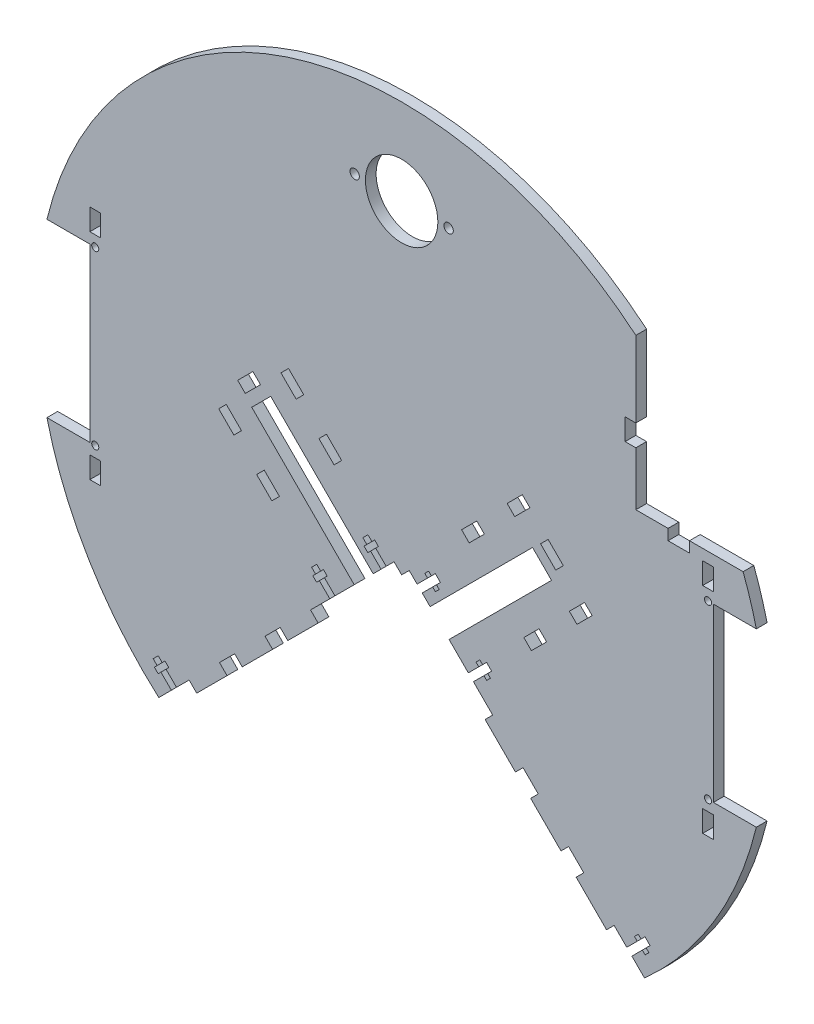
SolidWorks part; units mm, degrees
ref_plane "Front Plane" through (0, 0, 0) normal (0, 0, 1) x (1, 0, 0)
ref_plane "Top Plane" through (0, 0, 0) normal (0, 1, 0) x (1, 0, 0)
ref_plane "Right Plane" through (0, 0, 0) normal (1, 0, 0) x (0, 0, -1)
sketch "Sketch1" plane through (0, 0, 0) normal (0, 0, 1) x (1, 0, 0)
  circle A0 centre (0, 0) radius 215.9
  dimension "D1" = 431.8
extrude "Base Plate Extrusion" add sketch "Sketch1" along normal blind 6.35
sketch "Sketch2" plane through (0, 0, 6.35) normal (0, 0, 1) x (1, 0, 0)
  line L0 (0, 0) -> (0, -230.9791) construction
  line L1 (0, -17.4608) -> (143.6841, -161.1449)
  line L2 (0, -17.4608) -> (-143.6841, -161.1449)
  circle A1 centre (0, 0) radius 215.9 construction
  arc A2 (143.6841, -161.1449) -> (-143.6841, -161.1449) centre (0, 0) cw
  dimension "D1" = 90
  dimension "D2" = 203.2
extrude "V Funnel Cut" cut sketch "Sketch2" against normal through all
sketch "Sketch3" plane through (0, 0, 6.35) normal (0, 0, 1) x (1, 0, 0)
  line L0 (0, 0) -> (251.7982, 0) construction
  line L1 (209.8384, 50.8) -> (184.4384, 50.8)
  line L2 (209.8384, 50.8) -> (209.8384, -50.8)
  line L3 (209.8384, -50.8) -> (184.4384, -50.8)
  line L4 (184.4384, 50.8) -> (184.4384, -50.8)
  arc A0 (143.6841, -161.1449) -> (-143.6841, -161.1449) centre (0, 0) ccw construction
  arc A1 (209.8384, 50.8) -> (209.8384, -50.8) centre (0, 0) cw
  arc M7 (143.6841, -161.1449) -> (-143.6841, -161.1449) centre (0, 0) ccw
  dimension "D1" = 25.4
  dimension "D2" = 101.6
extrude "Wheel Track Cut" cut sketch "Sketch3" against normal through all contours L2 L0 A1 | L4 L0 L2 L1 | L0 L4 L3 L2 | L0 L2 M7 region at (197.1384, 25.4, 6.35) region at (197.1384, -25.4, 6.35) region at (212.266, 19.0862, 6.35) region at (212.266, -19.0862, 6.35)
mirror "Wheel Track Cut Mirror" about plane through (0, 0, 0) normal (1, 0, 0) of "Wheel Track Cut"
sketch "Sketch4" plane through (0, 0, 6.35) normal (0, 0, 1) x (1, 0, 0)
  line L0 (88.68, 15.0926) -> (77.4547, 26.3179)
  line L1 (88.68, 15.0926) -> (28.0633, -45.5241)
  line L2 (77.4547, 26.3179) -> (16.838, -34.2988)
  line L3 (28.0633, -45.5241) -> (16.838, -34.2988)
  line L4 (84.3174, 21.9553) -> (56.956, -5.4061) construction
  line L5 (65.1069, -1.7454) -> (69.5826, 2.7303) construction
  line L6 (65.0924, 7.2204) -> (60.6167, 2.7447) construction
  line L7 (143.6841, -161.1449) -> (0, -17.4608) construction
  dimension "D1" = 15.875
  dimension "D2" = 85.725
extrude "Cut-Extrude3" cut sketch "Sketch4" against normal through all
sketch "Sketch5" plane through (0, 0, 6.35) normal (0, 0, 1) x (1, 0, 0)
  line L0 (-4.4901, -21.951) -> (0, -17.4608)
  line L1 (-4.4901, -21.951) -> (0, -26.4411)
  line L2 (0, -17.4608) -> (4.4901, -21.951)
  line L3 (0, -26.4411) -> (4.4901, -21.951)
  line L4 (0, -17.4608) -> (-143.6841, -161.1449) construction
  line L6 (4.4901, -21.951) -> (0, -26.4411) construction
  dimension "D1" = 6.35
extrude "Boss-Extrude2" add sketch "Sketch5" against normal up to surface (6.35 mm away) up to face at (14.0691, -14.8765, 0)
mirror "Mirror2" about plane through (0, 0, 0) normal (1, 0, 0) of "Cut-Extrude3"
sketch "Sketch6" plane through (8.7304, -8.7304, 0) normal (0.7071, -0.7071, 0) x (0, 0, -1)
  line L0 (-6.35, -52.0342) -> (-6.35, -215.5467) construction
  line L1 (-6.35, -190.1467) -> (0, -190.1467)
  line L2 (-6.35, -190.1467) -> (-6.35, -164.7467)
  line L3 (-6.35, -164.7467) -> (0, -164.7467)
  line L4 (0, -190.1467) -> (0, -164.7467)
  line L5 (0, -52.0342) -> (0, -215.5467) construction
  dimension "D1" = 25.4
  dimension "D2" = 25.4
extrude "Boss-Extrude3" add sketch "Sketch6" along normal blind 6.35
pattern_linear "LPattern1" count 3 spacing 38.1 along (0.7071, 0.7071, 0) of "Boss-Extrude3"
sketch "Sketch7" plane through (-8.7304, -8.7304, 0) normal (-0.7071, -0.7071, 0) x (0, 0, 1)
  line L0 (6.35, -215.5467) -> (6.35, -52.0342) construction
  line L1 (6.35, -164.7467) -> (0, -164.7467)
  line L2 (6.35, -164.7467) -> (6.35, -190.1467)
  line L3 (6.35, -190.1467) -> (0, -190.1467)
  line L4 (0, -164.7467) -> (0, -190.1467)
  line L5 (0, -215.5467) -> (0, -52.0342) construction
  dimension "D1" = 25.4
  dimension "D2" = 25.4
extrude "Boss-Extrude4" add sketch "Sketch7" along normal blind 6.35
pattern_linear "LPattern2" count 3 spacing 38.1 along (-0.7071, 0.7071, 0) of "Boss-Extrude4"
sketch "Sketch8" plane through (0, 0, 0) normal (0, 0, -1) x (-1, 0, 0)
  line L0 (-72.2911, -22.4) -> (-81.2713, -13.4197)
  line L1 (-81.2713, -13.4197) -> (-85.7614, -17.9098)
  line L2 (-85.7614, -17.9098) -> (-76.7812, -26.8901)
  line L3 (-76.7812, -26.8901) -> (-72.2911, -22.4)
  line L4 (-99.2318, 4.5408) -> (-103.722, 0.0507)
  line L5 (-103.722, 0.0507) -> (-112.7022, 9.0309)
  line L6 (-112.7022, 9.0309) -> (-108.2121, 13.521)
  line L7 (-108.2121, 13.521) -> (-99.2318, 4.5408)
  line L8 (-95.6515, 26.0817) -> (-86.6712, 35.0619)
  line L9 (-86.6712, 35.0619) -> (-82.1811, 30.5718)
  line L10 (-82.1811, 30.5718) -> (-91.1613, 21.5915)
  line L11 (-91.1613, 21.5915) -> (-95.6515, 26.0817)
  line L12 (-66.9029, 36.8697) -> (-62.4128, 41.3598)
  line L13 (-62.4128, 41.3598) -> (-71.393, 50.3401)
  line L14 (-71.393, 50.3401) -> (-75.8832, 45.85)
  line L15 (-75.8832, 45.85) -> (-66.9029, 36.8697)
  line L16 (-48.9424, 18.9092) -> (-44.4523, 23.3993)
  line L17 (-44.4523, 23.3993) -> (-35.472, 14.4191)
  line L18 (-35.472, 14.4191) -> (-39.9621, 9.9289)
  line L19 (-39.9621, 9.9289) -> (-48.9424, 18.9092)
extrude "Cut-Extrude4" cut sketch "Sketch8" against normal blind 6.35
sketch "Sketch9" plane through (0, 0, 0) normal (0, 0, -1) x (-1, 0, 0)
  line L0 (-138.5621, 165.5698) -> (-138.5621, 76.2)
  line L1 (-138.5621, 76.2) -> (-202.0059, 76.2)
  line L2 (-132.2121, 76.2) -> (-157.6121, 76.2) construction
  line L3 (-138.5621, 152.4) -> (-138.5621, 120.65) construction
  arc A0 (209.8384, 50.8) -> (-209.8384, 50.8) centre (0, 0) ccw construction
  arc A1 (-202.0059, 76.2) -> (-138.5621, 165.5698) centre (0, 0) cw
extrude "Cut-Extrude5" cut sketch "Sketch9" against normal through all
sketch "Sketch10" plane through (0, 0, 0) normal (0, 0, -1) x (-1, 0, 0)
  line L0 (48.9424, 18.9092) -> (39.9621, 9.9289)
  line L1 (39.9621, 9.9289) -> (35.472, 14.4191)
  line L2 (35.472, 14.4191) -> (44.4523, 23.3993)
  line L3 (44.4523, 23.3993) -> (48.9424, 18.9092)
  line L4 (62.4128, 32.3796) -> (57.9227, 36.8697)
  line L5 (57.9227, 36.8697) -> (66.9029, 45.85)
  line L6 (66.9029, 45.85) -> (71.393, 41.3598)
  line L7 (71.393, 41.3598) -> (62.4128, 32.3796)
  line L8 (88.0065, 33.7266) -> (83.5144, 29.2385)
  line L9 (83.5144, 29.2385) -> (92.4966, 20.2562)
  line L10 (92.4966, 20.2562) -> (96.9868, 24.7464)
  line L11 (96.9868, 24.7464) -> (88.0065, 33.7266)
  line L12 (103.722, 9.0309) -> (94.7417, 0.0507)
  line L13 (94.7417, 0.0507) -> (99.2318, -4.4395)
  line L14 (99.2318, -4.4395) -> (108.2121, 4.5408)
  line L15 (108.2121, 4.5408) -> (103.722, 9.0309)
  line L16 (85.7614, -17.9098) -> (81.2713, -13.4197)
  line L17 (81.2713, -13.4197) -> (72.2911, -22.4)
  line L18 (72.2911, -22.4) -> (76.7812, -26.8901)
  line L19 (76.7812, -26.8901) -> (85.7614, -17.9098)
extrude "Cut-Extrude6" cut sketch "Sketch10" against normal blind 6.35
sketch "Sketch11" plane through (0, 0, 0) normal (0, 0, -1) x (-1, 0, 0)
  line L1 (184.4384, -69.85) -> (178.0884, -69.85)
  line L2 (184.4384, -69.85) -> (184.4384, -57.15)
  line L3 (184.4384, -57.15) -> (178.0884, -57.15)
  line L4 (178.0884, -69.85) -> (178.0884, -57.15)
  line L5 (184.4384, 57.15) -> (178.0884, 57.15)
  line L6 (184.4384, 57.15) -> (184.4384, 69.85)
  line L7 (184.4384, 69.85) -> (178.0884, 69.85)
  line L8 (178.0884, 57.15) -> (178.0884, 69.85)
  line L9 (-178.0884, -69.85) -> (-184.4384, -69.85)
  line L10 (-178.0884, -69.85) -> (-178.0884, -57.15)
  line L11 (-178.0884, -57.15) -> (-184.4384, -57.15)
  line L12 (-184.4384, -69.85) -> (-184.4384, -57.15)
  line L13 (-178.0884, 57.15) -> (-184.4384, 57.15)
  line L14 (-178.0884, 57.15) -> (-178.0884, 69.85)
  line L15 (-178.0884, 69.85) -> (-184.4384, 69.85)
  line L16 (-184.4384, 57.15) -> (-184.4384, 69.85)
extrude "Cut-Extrude7" cut sketch "Sketch11" against normal blind 6.35
sketch "Sketch12" plane through (0, 0, 0) normal (0, 0, -1) x (-1, 0, 0)
  line L0 (-202.0059, 76.2) -> (-138.5621, 76.2) construction
  line L1 (-157.6121, 69.85) -> (-170.284, 69.85)
  line L2 (-157.6121, 69.85) -> (-157.6121, 76.2)
  line L3 (-157.6121, 76.2) -> (-170.284, 76.2)
  line L4 (-170.284, 69.85) -> (-170.284, 76.2)
  line L5 (-138.5621, 76.2) -> (-138.5621, 165.5698) construction
  line L6 (-132.2121, 120.65) -> (-138.5621, 120.65)
  line L7 (-132.2121, 120.65) -> (-132.2121, 107.95)
  line L8 (-132.2121, 107.95) -> (-138.5621, 107.95)
  line L9 (-138.5621, 120.65) -> (-138.5621, 107.95)
  line L10 (-138.5621, 107.95) -> (-132.2121, 107.95) construction
extrude "Cut-Extrude8" cut sketch "Sketch12" against normal blind 6.35
sketch "Sketch13" plane through (0, 0, 6.35) normal (0, 0, 1) x (1, 0, 0)
  circle A0 centre (0, 165.1) radius 21.4313
  circle A1 centre (27.7813, 165.1) radius 2.7781
  circle A2 centre (-27.7812, 165.1) radius 2.7781
extrude "Cut-Extrude9" cut sketch "Sketch13" against normal through all
sketch "Sketch14" plane through (0, 0, 6.35) normal (0, 0, 1) x (1, 0, 0)
  line L0 (184.4384, 48.6664) -> (178.0884, 52.9336) construction
  line L1 (184.4384, 50.8) -> (184.4384, -50.8) construction
  line L2 (178.0884, 48.6664) -> (184.4384, 48.6664) construction
  line L3 (184.4384, 52.9336) -> (178.0884, 48.6664) construction
  line L4 (184.4384, -52.9336) -> (178.0884, -48.6664) construction
  line L5 (184.4384, -48.6664) -> (178.0884, -52.9336) construction
  line L6 (178.0884, -48.6664) -> (184.4384, -48.6664) construction
  circle A0 centre (181.2634, 50.8) radius 2.0955
  circle A1 centre (181.2634, -50.8) radius 2.0955
  dimension "D1" = 4.191
extrude "Cut-Extrude10" cut sketch "Sketch14" against normal through all
mirror "Mirror3" about plane through (0, 0, 0) normal (1, 0, 0) of "Cut-Extrude10"
sketch "Sketch15" plane through (0, 0, 6.35) normal (0, 0, 1) x (1, 0, 0)
  line L0 (-134.7038, -152.1647) -> (-152.6084, -134.2601) construction
  line L1 (-125.7236, -143.1844) -> (-143.6841, -161.1449) construction
  line L2 (-40.9724, -58.4333) -> (-60.7132, -38.6924) construction
  line L3 (-28.0633, -45.5241) -> (-53.8815, -71.3424) construction
  line L4 (-10.6641, -28.1249) -> (-27.2834, -11.5055) construction
  line L5 (-4.4901, -21.951) -> (-16.838, -34.2988) construction
  line B0 (-136.2125, -153.6734) -> (-133.1952, -150.656)
  line B1 (-141.6366, -142.2146) -> (-140.0022, -140.5801)
  line B2 (-140.0022, -140.5801) -> (-137.7571, -142.8252)
  line B3 (-137.7571, -142.8252) -> (-139.3915, -144.4596)
  line B4 (-139.3915, -144.4596) -> (-133.1952, -150.656)
  line B5 (-141.6366, -142.2146) -> (-143.9715, -139.8797)
  line B6 (-143.9715, -139.8797) -> (-146.9888, -142.8971)
  line B7 (-144.654, -145.2319) -> (-146.9888, -142.8971)
  line B8 (-142.4089, -147.477) -> (-136.2125, -153.6734)
  line B9 (-144.0433, -149.1114) -> (-142.4089, -147.477)
  line B10 (-146.2884, -146.8663) -> (-144.0433, -149.1114)
  line B11 (-144.654, -145.2319) -> (-146.2884, -146.8663)
  line B12 (-42.4811, -59.9419) -> (-39.4637, -56.9246)
  line B13 (-47.9052, -48.4831) -> (-46.2708, -46.8487)
  line B14 (-46.2708, -46.8487) -> (-44.0257, -49.0938)
  line B15 (-44.0257, -49.0938) -> (-45.6601, -50.7282)
  line B16 (-45.6601, -50.7282) -> (-39.4637, -56.9246)
  line B17 (-47.9052, -48.4831) -> (-50.24, -46.1483)
  line B18 (-50.24, -46.1483) -> (-53.2574, -49.1656)
  line B19 (-50.9225, -51.5005) -> (-53.2574, -49.1656)
  line B20 (-48.6775, -53.7456) -> (-42.4811, -59.9419)
  line B21 (-50.3119, -55.38) -> (-48.6775, -53.7456)
  line B22 (-52.5569, -53.1349) -> (-50.3119, -55.38)
  line B23 (-50.9225, -51.5005) -> (-52.5569, -53.1349)
  line B24 (-12.1727, -29.6336) -> (-9.1554, -26.6162)
  line B25 (-17.5968, -18.1748) -> (-15.9624, -16.5404)
  line B26 (-15.9624, -16.5404) -> (-13.7173, -18.7854)
  line B27 (-13.7173, -18.7854) -> (-15.3517, -20.4198)
  line B28 (-15.3517, -20.4198) -> (-9.1554, -26.6162)
  line B29 (-17.5968, -18.1748) -> (-19.9317, -15.8399)
  line B30 (-19.9317, -15.8399) -> (-22.949, -18.8573)
  line B31 (-20.6142, -21.1921) -> (-22.949, -18.8573)
  line B32 (-18.3691, -23.4372) -> (-12.1727, -29.6336)
  line B33 (-20.0035, -25.0716) -> (-18.3691, -23.4372)
  line B34 (-22.2486, -22.8265) -> (-20.0035, -25.0716)
  line B35 (-20.6142, -21.1921) -> (-22.2486, -22.8265)
sketch_block_instance "TSlot-1"
sketch_block "TSlot" parameters "D1"=3.302, "D2"=3.175
sketch_block_instance "TSlot-3"
sketch_block_instance "TSlot-4"
extrude "Cut-Extrude11" cut sketch "Sketch15" against normal through all
mirror "Mirror4" about plane through (0, 0, 0) normal (1, 0, 0) of "Cut-Extrude11"
